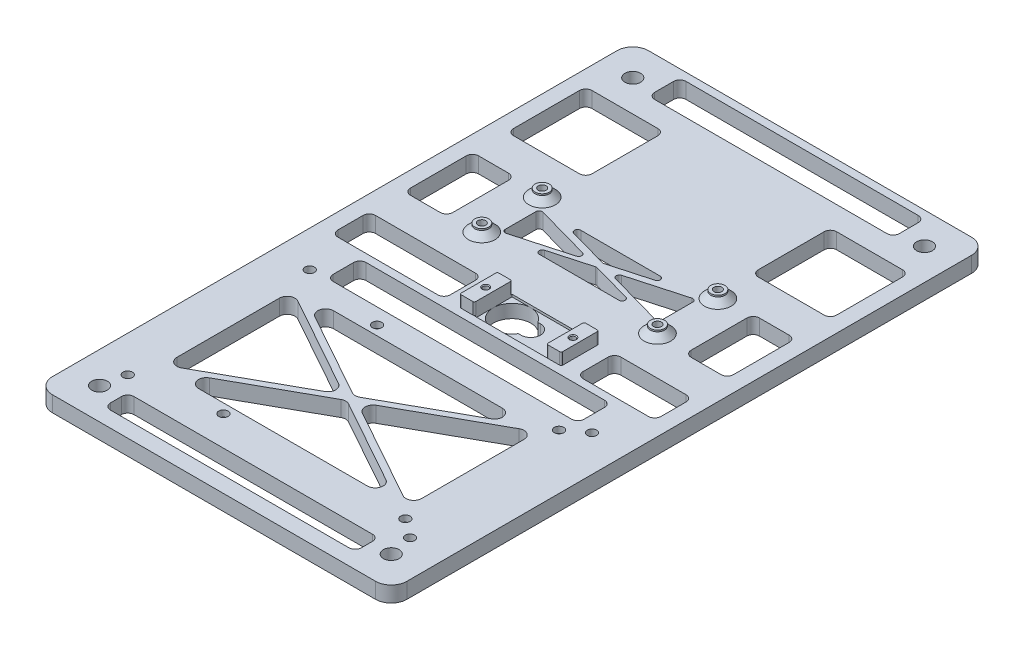
SolidWorks part; units mm, degrees
other "Markup1"
sketch "Sketch25" plane through (-56.5, 8.75, 95) normal (-0.8124, 0.5756, 0.0932) x (-0.5544, -0.812, 0.1827)
ref_plane "Front Plane" through (0, 0, 0) normal (0, 0, 1) x (1, 0, 0)
ref_plane "Top Plane" through (0, 0, 0) normal (0, 1, 0) x (1, 0, 0)
ref_plane "Right Plane" through (0, 0, 0) normal (1, 0, 0) x (0, 0, -1)
sketch "Sketch1" plane through (0, 0, 0) normal (0, 1, 0) x (1, 0, 0)
  line L0 (-56.5, -95) -> (-56.5, 95)
  line L1 (-46.5, -85) -> (46.5, -85) construction
  line L2 (-46.5, -85) -> (-46.5, 85) construction
  line L3 (-46.5, 85) -> (46.5, 85) construction
  line L4 (46.5, -85) -> (46.5, 85) construction
  line L5 (-46.5, -85) -> (46.5, 85) construction
  line L6 (-46.5, 85) -> (46.5, -85) construction
  line L7 (-56.5, 95) -> (56.5, 95)
  line L8 (56.5, -95) -> (56.5, 95)
  line L9 (-56.5, -95) -> (56.5, -95)
  circle A0 centre (46.5, 85) radius 2.5
  circle A1 centre (-46.5, 85) radius 2.5
  circle A2 centre (-46.5, -85) radius 2.5
  circle A3 centre (46.5, -85) radius 2.5
  point P0 (0, 0)
  dimension "D3" = 5
  dimension "D1" = 170
  dimension "D2" = 93
  dimension "D4" = 10
extrude "Boss-Extrude1" add sketch "Sketch1" along normal blind 5
fillet "Fillet1" radius 5 4 edges at (-56.5, 2.5, 95) (-56.5, 2.5, -95) (56.5, 2.5, -95) (56.5, 2.5, 95)
sketch "Sketch2" plane through (0, 5, 0) normal (0, 1, 0) x (1, 0, 0)
  line L0 (-39, -24) -> (-39, -73) construction
  line L1 (-39, -24) -> (39, -24) construction
  line L2 (-39, -20.5) -> (39, -20.5) construction
  line L3 (42.5, -48.5) -> (-39, -48.5) construction
  line L4 (-42.5, -24) -> (-42.5, -73) construction
  line L5 (42.5, -24) -> (42.5, -73) construction
  line L6 (-39, -76.5) -> (39, -76.5) construction
  line L7 (0, -20.5) -> (0, -1.8528) construction
  line L8 (-51.5, -95) -> (51.5, -95) construction
  circle A0 centre (39, -24) radius 1.5
  circle A1 centre (39, -73) radius 1.5
  arc A2 (-39, -20.5) -> (-42.5, -24) centre (-39, -24) ccw construction
  arc A3 (-39, -76.5) -> (-42.5, -73) centre (-39, -73) cw construction
  arc A4 (42.5, -24) -> (39, -20.5) centre (39, -24) ccw construction
  arc A5 (42.5, -73) -> (39, -76.5) centre (39, -73) cw construction
  circle A6 centre (-19, -24) radius 1.5
  circle A7 centre (-19, -73) radius 1.5
  point P14 (1.75, -48.5)
  dimension "D1" = 3
  dimension "D2" = 49
  dimension "D3" = 85
  dimension "D4" = 56
  dimension "D5" = 58
  dimension "D6" = 18.5
extrude "Cut-Extrude1" cut sketch "Sketch2" against normal blind 10
sketch "Sketch3" plane through (0, 5, 0) normal (0, 1, 0) x (1, 0, 0)
  line L0 (-45, -80) -> (45, -80) construction
  line L1 (-47.5, -77.5) -> (-47.5, -19.5) construction
  line L2 (-45, -17) -> (45, -17) construction
  line L3 (47.5, -77.5) -> (47.5, -19.5) construction
  line L4 (-47.5, -80) -> (47.5, -17) construction
  line L5 (-47.5, -17) -> (47.5, -80) construction
  line L6 (-51.5, -95) -> (51.5, -95) construction
  circle A0 centre (45, -19.5) radius 1.5
  circle A1 centre (45, -77.5) radius 1.5
  circle A2 centre (-45, -19.5) radius 1.5
  circle A3 centre (-45, -77.5) radius 1.5
  arc A4 (-47.5, -19.5) -> (-45, -17) centre (-45, -19.5) cw construction
  arc A5 (-45, -80) -> (-47.5, -77.5) centre (-45, -77.5) cw construction
  arc A6 (45, -80) -> (47.5, -77.5) centre (45, -77.5) ccw construction
  arc A7 (45, -17) -> (47.5, -19.5) centre (45, -19.5) cw construction
  point P0 (0, -48.5)
  dimension "D3" = 2.5
  dimension "D1" = 95
  dimension "D2" = 63
  dimension "D4" = 15
extrude "Cut-Extrude2" cut sketch "Sketch3" against normal blind 10
sketch "Sketch5" plane through (0, 5, 0) normal (0, 1, 0) x (1, 0, 0)
  line L1 (-38, -90) -> (38, -90)
  line L2 (-40, -88) -> (-40, -84.5)
  line L3 (-38, -82.5) -> (38, -82.5)
  line L4 (40, -88) -> (40, -84.5)
  line L5 (-40, -90) -> (40, -82.5) construction
  line L6 (-40, -82.5) -> (40, -90) construction
  circle A2 centre (-46.5, -85) radius 2.5 construction
  arc A3 (-38, -90) -> (-40, -88) centre (-38, -88) cw
  arc A4 (-40, -84.5) -> (-38, -82.5) centre (-38, -84.5) cw
  arc A5 (38, -82.5) -> (40, -84.5) centre (38, -84.5) cw
  arc A6 (38, -90) -> (40, -88) centre (38, -88) ccw
  point P0 (0, -86.25)
  dimension "D3" = 2
  dimension "D1" = 7.5
  dimension "D2" = 80
extrude "Cut-Extrude4" cut sketch "Sketch5" against normal blind 10
sketch "Sketch21" plane through (0, 5, 0) normal (0, 1, 0) x (1, 0, 0)
  line L4 (5.975, 2.875) -> (5.122, 2.875) construction
  line L5 (5.975, -2.875) -> (5.122, -2.875) construction
  line L6 (5.975, -3.125) -> (5.122, -3.125)
  line L7 (5.975, 3.125) -> (5.122, 3.125)
  arc A8 (4.9085, 2.9948) -> (4.9085, -2.9948) centre (0, 0) ccw construction
  arc A11 (5.975, -2.875) -> (5.975, 2.875) centre (5.975, 0) ccw construction
  arc A12 (4.9085, 2.9948) -> (5.122, 2.875) centre (5.122, 3.125) ccw construction
  arc A13 (5.122, -2.875) -> (4.9085, -2.9948) centre (5.122, -3.125) ccw construction
  arc A14 (5.122, 3.125) -> (5.122, -3.125) centre (0, 0) ccw
  arc A15 (5.122, -3.125) -> (5.122, -3.125) centre (5.122, -3.125) ccw
  arc A16 (5.975, -3.125) -> (5.975, 3.125) centre (5.975, 0) ccw
  arc A17 (5.122, 3.125) -> (5.122, 3.125) centre (5.122, 3.125) ccw
  dimension "D2" = 2.875
  dimension "D3" = 5.75
  dimension "D4" = 0.25
  dimension "D5" = 0.25
  dimension "D1" = 5.975
extrude "Cut-Extrude16" cut sketch "Sketch21" against normal through all
sketch "Sketch22" plane through (0, 5, 0) normal (0, 1, 0) x (1, 0, 0)
  line L0 (-6, 6) -> (-6, -6)
  line L1 (-6, 6) -> (17, 6)
  line L2 (-6, -6) -> (17, -6)
  line L3 (17, 6) -> (17, -6)
  arc A0 (5.122, 3.125) -> (5.122, -3.125) centre (0, 0) ccw construction
  dimension "D1" = 23
extrude "Cut-Extrude17" cut sketch "Sketch22" against normal blind 0.75
sketch "Sketch23" plane through (0, 5, 0) normal (0, 1, 0) x (1, 0, 0)
  line L0 (-6, 6) -> (-6, -6)
  line L1 (-6, 6) -> (-10.675, 6)
  line L2 (-6, -6) -> (-10.675, -6)
  line L3 (-10.675, 6) -> (-10.675, -6)
  line L4 (5.5, -6) -> (5.5, 6) construction
  line L5 (-6, -6) -> (17, -6) construction
  line L6 (17, 6) -> (-6, 6) construction
  line L7 (17, -6) -> (21.675, -6)
  line L8 (21.675, 6) -> (21.675, -6)
  line L9 (17, 6) -> (21.675, 6)
  line L10 (17, 6) -> (17, -6)
  circle A0 centre (-8.4, 0) radius 0.875
  circle A1 centre (19.4, 0) radius 0.875
  dimension "D2" = 1.75
  dimension "D1" = 4.675
  dimension "D3" = 2.4
extrude "Boss-Extrude5" add sketch "Sketch23" along normal blind 3.75
sketch "Sketch24" plane through (0, 5, 0) normal (0, 1, 0) x (1, 0, 0)
  circle A0 centre (19.4, 0) radius 0.875 construction
  circle A1 centre (-8.4, 0) radius 0.875 construction
  circle A2 centre (19.4, 0) radius 0.875
  circle A3 centre (-8.4, 0) radius 0.875
extrude "Cut-Extrude18" cut sketch "Sketch24" against normal blind 1.5
sketch "Sketch9" plane through (0, 5, 0) normal (0, 1, 0) x (1, 0, 0)
  line L0 (-48.1787, 10) -> (48.1787, 10)
  line L1 (-50, 11.8213) -> (-50, 38.1787)
  line L2 (-48.1787, 40) -> (48.1787, 40)
  line L3 (50, 11.8213) -> (50, 38.1787)
  line L4 (-50, 10) -> (50, 40) construction
  line L5 (-50, 40) -> (50, 10) construction
  arc A0 (48.1787, 40) -> (50, 38.1787) centre (48.1787, 38.1787) cw
  arc A1 (48.1787, 10) -> (50, 11.8213) centre (48.1787, 11.8213) ccw
  arc A2 (-48.1787, 10) -> (-50, 11.8213) centre (-48.1787, 11.8213) cw
  arc A3 (-50, 38.1787) -> (-48.1787, 40) centre (-48.1787, 38.1787) cw
  point P0 (0, 25)
  dimension "D4" = 1.8213
  dimension "D1" = 30
  dimension "D2" = 100
  dimension "D3" = 25
sketch "Sketch12" plane through (0, 5, 0) normal (0, 1, 0) x (1, 0, 0)
  line L1 (-51.5, 75) -> (-26.5, 75)
  line L2 (-51.5, 75) -> (-51.5, 50)
  line L3 (-51.5, 50) -> (-26.5, 50)
  line L4 (-26.5, 75) -> (-26.5, 50)
  line L6 (0, 0) -> (0, -22.2555) construction
  line L7 (26.5, 75) -> (26.5, 50)
  line L8 (51.5, 50) -> (26.5, 50)
  line L9 (51.5, 75) -> (51.5, 50)
  line L10 (51.5, 75) -> (26.5, 75)
  line L11 (-56.5, 90) -> (-56.5, -90) construction
  dimension "D1" = 25
  dimension "D2" = 25
  dimension "D3" = 50
  dimension "D4" = 5
extrude "Cut-Extrude9" cut sketch "Sketch12" against normal through all
sketch "Sketch15" plane through (0, 5, 0) normal (0, 1, 0) x (1, 0, 0)
  line L1 (-51.5, 6) -> (-15.675, 6)
  line L2 (-51.5, 6) -> (-51.5, -6)
  line L3 (-51.5, -6) -> (-15.675, -6)
  line L4 (-15.675, 6) -> (-15.675, -6)
  line L6 (-56.5, 90) -> (-56.5, -90) construction
  line L9 (26.675, 6) -> (51.5, 6)
  line L10 (26.675, 6) -> (26.675, -6)
  line L11 (26.675, -6) -> (51.5, -6)
  line L12 (51.5, 6) -> (51.5, -6)
  line L13 (56.5, -90) -> (56.5, 90) construction
  line L15 (17, 6) -> (-6, 6) construction
  line L16 (-6, -6) -> (17, -6) construction
  line L17 (21.675, -6) -> (21.675, 6) construction
  line L18 (-10.675, 6) -> (-10.675, -6) construction
  dimension "D1" = 5
  dimension "D2" = 5
  dimension "D3" = 5
  dimension "D4" = 5
extrude "Cut-Extrude11" cut sketch "Sketch15" against normal up to next
fillet "Fillet3" radius 2 16 edges at (-51.5, 2.5, 6) (-51.5, 2.5, -6) (-15.675, 2.5, -6) (-15.675, 2.5, 6) (51.5, 2.5, -6) (26.675, 2.5, -6) (26.675, 2.5, 6) (51.5, 2.5, 6) (51.5, 2.5, -50) (51.5, 2.5, -75) (26.5, 2.5, -50) (26.5, 2.5, -75) (-26.5, 2.5, -50) (-51.5, 2.5, -50) (-51.5, 2.5, -75) (-26.5, 2.5, -75)
sketch "Sketch16" plane through (0, 0, 0) normal (0, -1, 0) x (1, 0, 0)
  line L0 (-42, 64.8229) -> (-42, 32.1771)
  line L1 (-42.5, 70.5) -> (36.5, 70.5) construction
  line L2 (-42.5, 70.5) -> (-42.5, 26.5) construction
  line L3 (-42.5, 26.5) -> (36.5, 26.5) construction
  line L4 (36.5, 70.5) -> (36.5, 26.5) construction
  line L5 (-42.5, 70.5) -> (36.5, 26.5) construction
  line L6 (-42.5, 26.5) -> (36.5, 70.5) construction
  line L7 (-38.2835, 29.993) -> (-8.9766, 46.3159)
  line L8 (-8.9766, 50.6841) -> (-38.2835, 67.007)
  line L9 (-31.1371, 31.6841) -> (-4.2165, 46.6778)
  line L10 (-1.7835, 46.6778) -> (25.1371, 31.6841)
  line L11 (23.9206, 27) -> (-29.9206, 27)
  line L12 (-3, 48.5) -> (-3, 70.5) construction
  line L13 (-3, 48.5) -> (36.5, 48.5) construction
  line L14 (32.2835, 29.993) -> (2.9766, 46.3159)
  line L15 (36, 64.8229) -> (36, 32.1771)
  line L16 (2.9766, 50.6841) -> (32.2835, 67.007)
  line L17 (-1.7835, 50.3222) -> (25.1371, 65.3159)
  line L18 (-31.1371, 65.3159) -> (-4.2165, 50.3222)
  line L19 (23.9206, 70) -> (-29.9206, 70)
  line L20 (-33.5875, -28) -> (-33.5875, -6) construction
  line L26 (-28, -37.625) -> (28, -37.625) construction
  line L27 (-28, -37.625) -> (-28, -18.375) construction
  line L28 (-49.5, -6) -> (-17.675, -6) construction
  line L29 (-33.5875, -28) -> (-33.5875, -50) construction
  line L30 (51.5, -95) -> (-51.5, -95) construction
  line L31 (-37, -82.5) -> (37, -82.5)
  line L32 (-39, -84.5) -> (-39, -90.5)
  line L33 (-37, -92.5) -> (37, -92.5)
  line L34 (39, -84.5) -> (39, -90.5)
  line L35 (-39, -82.5) -> (39, -92.5) construction
  line L36 (-39, -92.5) -> (39, -82.5) construction
  line L37 (-28.5, -75) -> (-49.5, -75) construction
  line L44 (-49.5, -50) -> (-28.5, -50) construction
  line L63 (-28, -18.375) -> (28, -18.375) construction
  line L64 (28, -37.625) -> (28, -18.375) construction
  line L65 (-28, -37.625) -> (28, -18.375) construction
  line L66 (-28, -18.375) -> (28, -37.625) construction
  circle A0 centre (-45, 77.5) radius 1.5 construction
  circle A1 centre (39, 73) radius 1.5 construction
  circle A2 centre (39, 24) radius 1.5 construction
  circle A3 centre (-19, 73) radius 1.5 construction
  arc A4 (23.9206, 27) -> (25.1371, 31.6841) centre (23.9206, 29.5) ccw
  arc A5 (-1.7835, 46.6778) -> (-4.2165, 46.6778) centre (-3, 44.4938) ccw
  arc A6 (-29.9206, 27) -> (-31.1371, 31.6841) centre (-29.9206, 29.5) cw
  arc A7 (-42, 32.1771) -> (-38.2835, 29.993) centre (-39.5, 32.1771) ccw
  arc A8 (-8.9766, 46.3159) -> (-8.9766, 50.6841) centre (-10.193, 48.5) ccw
  arc A9 (-38.2835, 67.007) -> (-42, 64.8229) centre (-39.5, 64.8229) ccw
  arc A10 (36, 32.1771) -> (32.2835, 29.993) centre (33.5, 32.1771) cw
  arc A11 (2.9766, 46.3159) -> (2.9766, 50.6841) centre (4.193, 48.5) cw
  arc A12 (32.2835, 67.007) -> (36, 64.8229) centre (33.5, 64.8229) cw
  arc A13 (-1.7835, 50.3222) -> (-4.2165, 50.3222) centre (-3, 52.5062) cw
  arc A14 (23.9206, 70) -> (25.1371, 65.3159) centre (23.9206, 67.5) cw
  arc A15 (-29.9206, 70) -> (-31.1371, 65.3159) centre (-29.9206, 67.5) ccw
  circle A16 centre (-46.5, -85) radius 2.5 construction
  circle A17 centre (46.5, -85) radius 2.5 construction
  arc A30 (-39, -90.5) -> (-37, -92.5) centre (-37, -90.5) ccw
  arc A31 (37, -92.5) -> (39, -90.5) centre (37, -90.5) ccw
  arc A32 (39, -84.5) -> (37, -82.5) centre (37, -84.5) ccw
  arc A33 (-37, -82.5) -> (-39, -84.5) centre (-37, -84.5) ccw
  circle A34 centre (-28, -18.375) radius 1.25
  circle A35 centre (28, -18.375) radius 1.25
  circle A36 centre (28, -37.625) radius 1.25
  circle A37 centre (-28, -37.625) radius 1.25
  point P4 (-3, 48.5)
  point P52 (0, -28)
  point P69 (0, -87.5)
  dimension "D3" = 2.5
  dimension "D4" = 2.5
  dimension "D11" = 2.5
  dimension "D18" = 2
  dimension "D19" = 2
  dimension "D20" = 2.5
  dimension "D1" = 2.5
  dimension "D2" = 2.5
  dimension "D5" = 1
  dimension "D6" = 1
  dimension "D7" = 1
  dimension "D8" = 1
  dimension "D9" = 1
  dimension "D10" = 1
  dimension "D12" = 56
  dimension "D13" = 19.25
  dimension "D14" = 2.5
  dimension "D15" = 7.5
  dimension "D16" = 7.5
  dimension "D17" = 7.5
extrude "Cut-Extrude12" cut sketch "Sketch16" against normal up to next
sketch "Sketch17" plane through (0, 5, 0) normal (0, 1, 0) x (1, 0, 0)
  line L0 (0, 0) -> (0, 50000) construction
  line L1 (-40, 38.875) -> (-49.5, 38.875)
  line L2 (-38, 36.875) -> (-38, 19.125)
  line L3 (-40, 17.125) -> (-49.5, 17.125)
  line L4 (-51.5, 36.875) -> (-51.5, 19.125)
  line L5 (-38, 38.875) -> (-51.5, 17.125) construction
  line L6 (-38, 17.125) -> (-51.5, 38.875) construction
  line L7 (-51.5, 73) -> (-51.5, 52) construction
  line L8 (40, 17.125) -> (49.5, 17.125)
  line L9 (51.5, 36.875) -> (51.5, 19.125)
  line L10 (40, 38.875) -> (49.5, 38.875)
  line L11 (38, 36.875) -> (38, 19.125)
  circle A0 centre (-28, 18.375) radius 1.25 construction
  circle A1 centre (-28, 37.625) radius 1.25 construction
  arc A2 (-51.5, 19.125) -> (-49.5, 17.125) centre (-49.5, 19.125) ccw
  arc A3 (-40, 17.125) -> (-38, 19.125) centre (-40, 19.125) ccw
  arc A4 (-38, 36.875) -> (-40, 38.875) centre (-40, 36.875) ccw
  arc A5 (-49.5, 38.875) -> (-51.5, 36.875) centre (-49.5, 36.875) ccw
  arc A6 (51.5, 19.125) -> (49.5, 17.125) centre (49.5, 19.125) cw
  arc A7 (49.5, 38.875) -> (51.5, 36.875) centre (49.5, 36.875) cw
  arc A8 (40, 17.125) -> (38, 19.125) centre (40, 19.125) cw
  arc A9 (38, 36.875) -> (40, 38.875) centre (40, 36.875) cw
  point P4 (-44.75, 28)
  dimension "D2" = 2
  dimension "D1" = 10
extrude "Cut-Extrude13" cut sketch "Sketch17" against normal up to next
sketch "Sketch18" plane through (0, 5, 0) normal (0, 1, 0) x (1, 0, 0)
  line L0 (-25, 32.6293) -> (-25, 22.8516)
  line L1 (-25.5, 35.125) -> (25.5, 35.125) construction
  line L2 (-25.5, 35.125) -> (-25.5, 20.875) construction
  line L3 (-25.5, 20.875) -> (25.5, 20.875) construction
  line L4 (25.5, 35.125) -> (25.5, 20.875) construction
  line L5 (-25.5, 35.125) -> (25.5, 20.875) construction
  line L6 (-25.5, 20.875) -> (25.5, 35.125) construction
  line L7 (-23.7309, 21.8885) -> (-6.2339, 26.7773)
  line L8 (-6.2339, 28.7035) -> (-23.7309, 33.5924)
  line L9 (-12.6995, 34.625) -> (12.6995, 34.625)
  line L10 (12.9686, 32.6619) -> (0.2691, 29.1135)
  line L11 (-0.2691, 29.1135) -> (-12.9686, 32.6619)
  line L12 (0, 28) -> (0, 20.875) construction
  line L13 (0, 28) -> (25.5, 28) construction
  line L14 (23.7309, 21.8885) -> (6.2339, 26.7773)
  line L15 (25, 32.6293) -> (25, 22.8516)
  line L16 (6.2339, 28.7035) -> (23.7309, 33.5924)
  line L17 (12.9686, 23.3381) -> (0.2691, 26.8865)
  line L18 (-12.6995, 21.375) -> (12.6995, 21.375)
  line L19 (-0.2691, 26.8865) -> (-12.9686, 23.3381)
  line L20 (-49.5, -6) -> (-17.675, -6) construction
  line L21 (-38, -8.5) -> (38, -8.5)
  line L22 (-40, -10.5) -> (-40, -17)
  line L23 (-38, -19) -> (38, -19)
  line L24 (40, -10.5) -> (40, -17)
  line L25 (-40, -8.5) -> (40, -19) construction
  line L26 (-40, -19) -> (40, -8.5) construction
  circle A0 centre (-28, 37.625) radius 1.25 construction
  circle A1 centre (-28, 18.375) radius 1.25 construction
  circle A2 centre (28, 37.625) radius 1.25 construction
  arc A3 (-0.2691, 29.1135) -> (0.2691, 29.1135) centre (0, 30.0766) ccw
  arc A4 (12.9686, 32.6619) -> (12.6995, 34.625) centre (12.6995, 33.625) ccw
  arc A5 (-12.6995, 34.625) -> (-12.9686, 32.6619) centre (-12.6995, 33.625) ccw
  arc A6 (-25, 22.8516) -> (-23.7309, 21.8885) centre (-24, 22.8516) ccw
  arc A7 (-6.2339, 26.7773) -> (-6.2339, 28.7035) centre (-6.503, 27.7404) ccw
  arc A8 (-23.7309, 33.5924) -> (-25, 32.6293) centre (-24, 32.6293) ccw
  arc A9 (25, 22.8516) -> (23.7309, 21.8885) centre (24, 22.8516) cw
  arc A10 (6.2339, 26.7773) -> (6.2339, 28.7035) centre (6.503, 27.7404) cw
  arc A11 (23.7309, 33.5924) -> (25, 32.6293) centre (24, 32.6293) cw
  arc A12 (12.9686, 23.3381) -> (12.6995, 21.375) centre (12.6995, 22.375) cw
  arc A13 (-0.2691, 26.8865) -> (0.2691, 26.8865) centre (0, 25.9234) cw
  arc A14 (-12.6995, 21.375) -> (-12.9686, 23.3381) centre (-12.6995, 22.375) cw
  circle A15 centre (-45, -19.5) radius 1.5 construction
  circle A16 centre (45, -19.5) radius 1.5 construction
  circle A17 centre (39, -24) radius 1.5 construction
  arc A18 (38, -8.5) -> (40, -10.5) centre (38, -10.5) cw
  arc A19 (40, -17) -> (38, -19) centre (38, -17) cw
  arc A20 (-38, -19) -> (-40, -17) centre (-38, -17) cw
  arc A21 (-38, -8.5) -> (-40, -10.5) centre (-38, -10.5) ccw
  point P4 (0, 28)
  point P54 (0, -13.75)
  dimension "D11" = 1
  dimension "D13" = 5
  dimension "D16" = 2
  dimension "D1" = 2.5
  dimension "D2" = 2.5
  dimension "D3" = 2.5
  dimension "D4" = 2.5
  dimension "D5" = 1
  dimension "D6" = 1
  dimension "D7" = 1
  dimension "D8" = 1
  dimension "D9" = 1
  dimension "D10" = 1
  dimension "D12" = 5
  dimension "D14" = 5
  dimension "D15" = 2.5
extrude "Cut-Extrude14" cut sketch "Sketch18" against normal through all
sketch "Sketch19" plane through (0, 5, 0) normal (0, 1, 0) x (1, 0, 0)
  circle A0 centre (-28, 18.375) radius 1.25 construction
  circle A1 centre (28, 18.375) radius 1.25 construction
  circle A2 centre (28, 37.625) radius 1.25 construction
  circle A3 centre (-28, 37.625) radius 1.25 construction
  circle A4 centre (-28, 18.375) radius 1.25
  circle A5 centre (28, 18.375) radius 1.25
  circle A6 centre (28, 37.625) radius 1.25
  circle A7 centre (-28, 37.625) radius 1.25
  circle A8 centre (-28, 37.625) radius 2.25
  circle A9 centre (-28, 18.375) radius 2.25
  circle A10 centre (28, 37.625) radius 2.25
  circle A11 centre (28, 18.375) radius 2.25
  dimension "D1" = 1
  dimension "D2" = 1
  dimension "D3" = 1
  dimension "D4" = 1
extrude "Boss-Extrude4" add sketch "Sketch19" along normal blind 2.5
chamfer "Chamfer1" distance 2 angle 45 4 edges at (-28, 5, -35.375) (-28, 5, -16.125) (28, 5, -16.125) (28, 5, -35.375)
sketch "Sketch20" plane through (0, 0, 0) normal (0, -1, 0) x (1, 0, 0)
  circle A0 centre (-19, 73) radius 2.5
  circle A1 centre (-19, 24) radius 2.5
  circle A2 centre (39, 24) radius 2.5
  circle A4 centre (39, 73) radius 2.5
  dimension "D1" = 5
extrude "Cut-Extrude15" cut sketch "Sketch20" against normal blind 3
fillet "Fillet4" radius 0.5 8 edges at (21.675, 6.875, -6) (17, 6.875, -6) (-10.675, 6.875, -6) (-6, 6.875, -6) (17, 6.875, 6) (-6, 6.875, 6) (21.675, 6.875, 6) (-10.675, 6.875, 6)
chamfer "Chamfer2" distance 0.25 angle 45 2 edges at (-8.4, 8.75, 0.875) (19.4, 8.75, -0.875)
